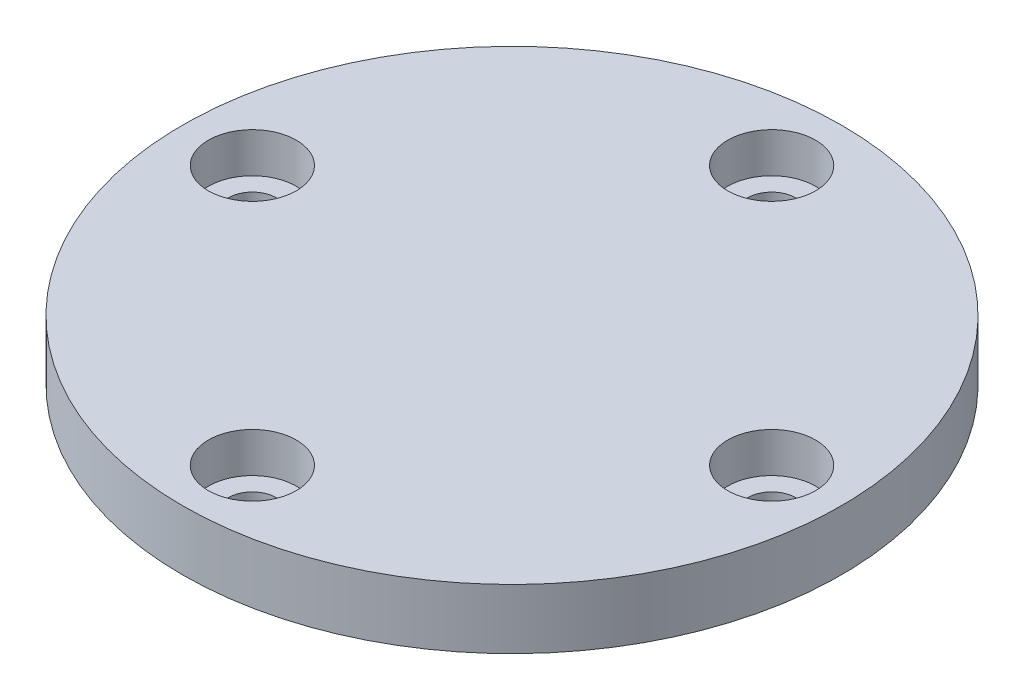
SolidWorks part; units mm, degrees
material "1060 Alloy"
ref_plane "Front Plane" through (0, 0, 0) normal (0, 0, 1) x (1, 0, 0)
ref_plane "Top Plane" through (0, 0, 0) normal (0, 1, 0) x (1, 0, 0)
ref_plane "Right Plane" through (0, 0, 0) normal (1, 0, 0) x (0, 0, -1)
sketch "Sketch1" plane through (0, 0, 0) normal (0, 1, 0) x (1, 0, 0)
  circle A0 centre (0, 0) radius 16.5
  dimension "D1" = 33
extrude "Boss-Extrude1" add sketch "Sketch1" along normal blind 3
sketch "Sketch7" plane through (0, 3, 0) normal (0, 1, 0) x (1, 0, 0)
  circle A0 centre (0, -10.25) radius 0.25
  circle A1 centre (0, 0) radius 9.8
  dimension "D1" = 0.5
  dimension "D2" = 10.25
  dimension "D3" = 19.6
sketch "Sketch8" plane through (0, 3, 0) normal (0, 1, 0) x (1, 0, 0)
  line L0 (0, 0) -> (13.2071, 13.2071) construction
  circle A0 centre (7.7782, 7.7782) radius 1
  dimension "D1" = 2
  dimension "D2" = 11
sketch "Sketch9" plane through (0, 3, 0) normal (0, 1, 0) x (1, 0, 0)
  circle A0 centre (0, 0) radius 11
  dimension "D1" = 22
hole_wizard "CBORE for M2 SHCS1" positions "Sketch13" profile "Sketch14" counterbore size "M2" standard "ANSI Metric" end condition through all
sketch "Sketch13" plane through (0, 3, 0) normal (0, 1, 0) x (1, 0, 0)
  circle A0 centre (0, 0) radius 11 construction
  point P0 (-13, 0)
  dimension "D1" = 13
sketch "Sketch14" plane through (-13, 3, 0) normal (1, 0, 0) x (0, 0, 1)
  line L0 (0, 0) -> (0, 3)
  line L1 (0, 3) -> (1.2, 3)
  line L3 (1.2, 3) -> (1.2, 2)
  line L4 (1.2, 2) -> (2.2, 2)
  line L5 (2.2, 2) -> (2.2, 0)
  line L7 (2.2, 0) -> (0, 0)
  line L11 (0, -6.35) -> (0, 107.95) construction
  dimension "Thru Hole Dia." = 2.4
  dimension "Thru Hole Depth" = 3
  dimension "C'Bore Dia." = 4.4
  dimension "C'Bore Depth" = 2
pattern_circular "CirPattern1" count 4 over 360 about axis through (0, 3, 0) along (0, 1, 0) of "CBORE for M2 SHCS1"
sketch "Sketch15" plane through (0, 0, 0) normal (0, -1, 0) x (1, 0, 0)
  circle A0 centre (6, 0) radius 0.5
  dimension "D2" = 1
  dimension "D1" = 6
extrude "Cut-Extrude1" cut sketch "Sketch15" against normal blind 1.5
